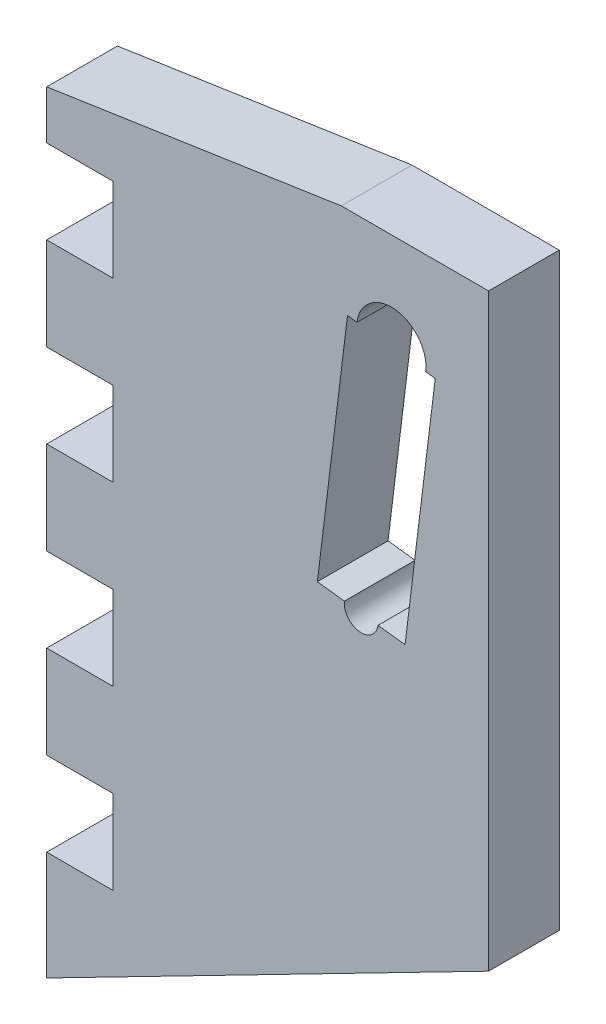
SolidWorks part; units mm, degrees
material "Thornel VCB-20 Carbon Cloth"
ref_plane "Front Plane" through (0, 0, 0) normal (0, 0, 1) x (1, 0, 0)
ref_plane "Top Plane" through (0, 0, 0) normal (0, 1, 0) x (1, 0, 0)
ref_plane "Right Plane" through (0, 0, 0) normal (1, 0, 0) x (0, 0, -1)
sketch "Sketch1" plane through (0, 0, 0) normal (0, 0, 1) x (1, 0, 0)
  line L0 (0, 0) -> (-38.1, 0)
  line L1 (0, 0) -> (0, -50.8)
  line L2 (-38.1, 0) -> (-38.1, -8.001)
  line L3 (-38.1, -8.001) -> (-32.385, -8.001)
  line L4 (-32.385, -8.001) -> (-32.385, -15.24)
  line L5 (-32.385, -15.24) -> (-38.1, -15.24)
  line L6 (-38.1, -45.72) -> (-38.1, -70.358)
  line L7 (-38.1, -15.24) -> (-38.1, -23.241)
  line L8 (-38.1, -23.241) -> (-32.385, -23.241)
  line L9 (-32.385, -23.241) -> (-32.385, -30.48)
  line L10 (-32.385, -30.48) -> (-38.1, -30.48)
  line L11 (-38.1, -30.48) -> (-38.1, -38.481)
  line L12 (-38.1, -38.481) -> (-32.385, -38.481)
  line L13 (-32.385, -38.481) -> (-32.385, -45.72)
  line L14 (-32.385, -45.72) -> (-38.1, -45.72)
  line L15 (-38.1, -70.358) -> (0, -50.8)
  circle A0 centre (-8.382, -8.382) radius 2.9845
  dimension "D9" = 5.969
  dimension "D1" = 38.1
  dimension "D2" = 50.8
  dimension "D3" = 8.001
  dimension "D4" = 7.239
  dimension "D6" = 5.715
  dimension "D8" = 70.358
  dimension "D12" = 8.382
  dimension "D13" = 8.382
  dimension "D7" = 3
extrude "Boss-Extrude1" add sketch "Sketch1" along normal blind 6.096 contours L6 L15 L1 L0 L2 L3 L4 L5 L7 L8 L9 L10 L11 L12 L13 L14 A0 region at (-19.3537, -31.0529, 0)
sketch "Sketch2" plane through (0, 0, 0) normal (0, 0, -1) x (-1, 0, 0)
  line L5 (38.1, 0) -> (12.7, 0)
  line L6 (0, 0) -> (38.1, 0) construction
  line L7 (12.7, 0) -> (38.1, -3.81)
  line L8 (38.1, 0) -> (38.1, -8.001) construction
  line L9 (38.1, -3.81) -> (38.1, 0)
  dimension "D1" = 25.4
  dimension "D2" = 3.81
extrude "Cut-Extrude1" cut sketch "Sketch2" against normal blind 8.636
sketch "Sketch4" plane through (0, 0, 6.096) normal (0, 0, 1) x (1, 0, 0)
  line L0 (-38.1, -45.72) -> (-38.1, -53.721)
  line L1 (-38.1, -45.72) -> (-38.1, -70.358) construction
  line L2 (-38.1, -53.721) -> (-32.385, -53.721)
  line L3 (-32.385, -53.721) -> (-32.385, -60.96)
  line L4 (-32.385, -60.96) -> (-38.1, -60.96)
  line L5 (-38.1, -60.96) -> (-38.1, -53.721)
  line M18 (-38.1, -45.72) -> (-38.1, -70.358)
  dimension "D1" = 7.239
  dimension "D2" = 5.715
  dimension "D3" = 5.715
  dimension "D4" = 8.001
extrude "Cut-Extrude2" cut sketch "Sketch4" against normal through all contours L4 L3 L2 M18 region at (-35.2425, -57.3405, 6.096)
sketch "Sketch5" plane through (0, 0, 0) normal (0, 0, -1) x (-1, 0, 0)
  line L0 (8.382, -8.382) -> (10.9822, -29.559) construction
  line L1 (8.382, -8.382) -> (8.382, -39.2411) construction
  circle A0 centre (8.382, -8.382) radius 2.9845 construction
  circle A1 centre (10.9822, -29.559) radius 1.4605
  dimension "D3" = 2.921
  dimension "D1" = 21.336
  dimension "D2" = 7
extrude "Cut-Extrude4" cut sketch "Sketch5" against normal up to surface (6.096 mm away) up to face at (-5.3975, -8.382, 6.096)
sketch "Sketch6" plane through (0, 0, 6.096) normal (0, 0, 1) x (1, 0, 0)
  line L0 (-5.2307, -8.7689) -> (-4.6004, -8.8463)
  line L1 (-11.5333, -7.9951) -> (-12.1636, -7.9177)
  line L6 (-14.7638, -29.0946) -> (-12.6209, -29.3578)
  line L7 (-4.6004, -8.8463) -> (-7.2006, -30.0233)
  line L8 (-12.1636, -7.9177) -> (-14.7638, -29.0946)
  line L10 (-9.3435, -29.7602) -> (-7.2006, -30.0233)
  line L11 (-12.6209, -29.3578) -> (-9.3435, -29.7602)
  line L12 (-11.5333, -7.9951) -> (-5.2307, -8.7689)
  dimension "D5" = 21.336
  dimension "D2" = 0.635
  dimension "D3" = 0.635
extrude "Cut-Extrude5" cut sketch "Sketch6" against normal up to surface (6.096 mm away) up to face at (-12.4427, -29.559, 0)
